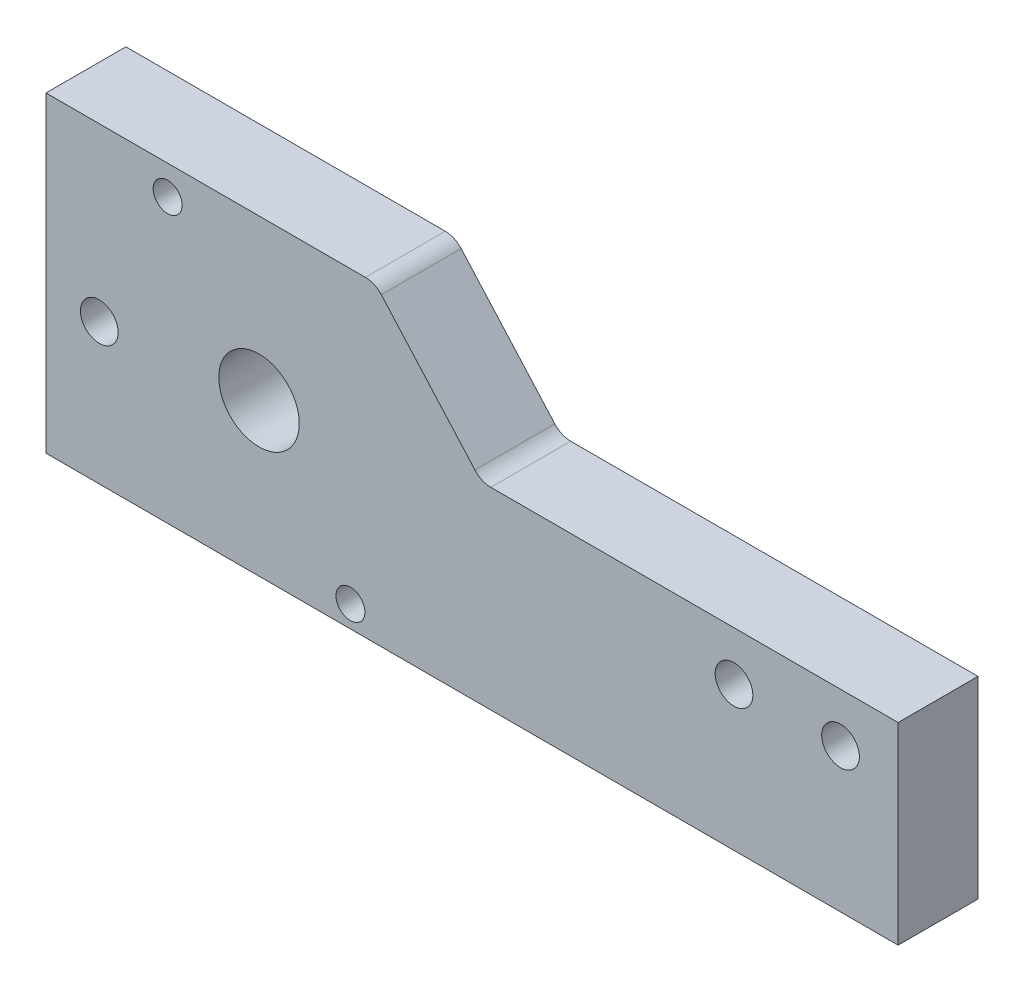
SolidWorks part; units mm, degrees
ref_plane "Front Plane" through (0, 0, 0) normal (0, 0, 1) x (1, 0, 0)
ref_plane "Top Plane" through (0, 0, 0) normal (0, 1, 0) x (1, 0, 0)
ref_plane "Right Plane" through (0, 0, 0) normal (1, 0, 0) x (0, 0, -1)
sketch "Sketch1" plane through (0, 0, 0) normal (0, 0, 1) x (1, 0, 0)
  line L1 (50.8, -25.4) -> (-50.8, -25.4)
  line L2 (50.8, -25.4) -> (50.8, 25.4)
  line L3 (50.8, 25.4) -> (-50.8, 25.4)
  line L4 (-50.8, -25.4) -> (-50.8, 25.4)
  line L5 (50.8, -25.4) -> (-50.8, 25.4) construction
  line L6 (50.8, 25.4) -> (-50.8, -25.4) construction
  point P0 (0, 0)
  dimension "D1" = 101.6
  dimension "D2" = 50.8
extrude "Boss-Extrude1" add sketch "Sketch1" along normal blind 9.525
sketch "Sketch3" plane through (0, 0, 9.525) normal (0, 0, 1) x (1, 0, 0)
  line L0 (-36.298, 21.9139) -> (-14.502, -9.2139) construction
  line L1 (50.8, 25.4) -> (-50.8, 25.4) construction
  circle A0 centre (-25.4, 6.35) radius 19 construction
  point P8 (-36.298, 21.9139)
  point P9 (-14.502, -9.2139)
  dimension "D1" = 38
  dimension "D2" = 25.4
  dimension "D3" = 6.35
  dimension "D4" = 55
sketch "Sketch6" plane through (0, 0, 0) normal (0, 0, 1) x (1, 0, 0)
  line L0 (-50.8, 25.4) -> (-50.8, -25.4) construction
  line L1 (-50.8, -25.4) -> (50.8, -25.4) construction
  circle A0 centre (-25.4, 6.35) radius 4.8 construction
  circle A1 centre (-25.4, 6.35) radius 4.8
  point P8 (-27.0981, 10.6379)
  point P9 (-20.85, 7.9694)
  dimension "D1" = 9.6
  dimension "D2" = 25.4
  dimension "D4" = 9.6
  dimension "D3" = 31.75
extrude "Cut-Extrude1" cut sketch "Sketch6" along normal through all contours A1
hole_wizard "Tap Drill for #8-32 Tap1" positions "Sketch3" profile "Sketch5" hole size "#8-32" standard "ANSI Inch" end condition through all
sketch "Sketch5" plane through (-14.502, -9.2139, 9.525) normal (1, 0, 0) x (0, -1, 0)
  line L0 (0, 0) -> (0, 9.525)
  line L1 (0, 9.525) -> (1.7272, 9.525)
  line L2 (1.7272, 9.525) -> (1.7272, 0)
  line L5 (1.7272, 0) -> (0, 0)
  line L11 (0, -6.35) -> (0, 107.95) construction
  dimension "Thru Hole Dia." = 3.4544
  dimension "Thru Hole Depth" = 9.525
sketch "Sketch7" plane through (0, 0, 0) normal (0, 0, -1) x (-1, 0, 0)
  line L0 (-50.8, -25.4) -> (-50.8, 25.4) construction
  line L1 (50.8, -25.4) -> (-50.8, -25.4)
  line L2 (50.8, -25.4) -> (50.8, -6.35)
  line L3 (50.8, -6.35) -> (-50.8, -6.35)
  line L4 (-50.8, -25.4) -> (-50.8, -6.35)
  dimension "D1" = 19.05
hole_wizard "#8 Clearance Hole1" positions "Sketch8" profile "Sketch9" hole size "#8" standard "ANSI Inch" end condition through all
sketch "Sketch8" plane through (0, 0, 9.525) normal (0, 0, 1) x (1, 0, 0)
  circle A0 centre (31.2318, 5.3435) radius 2.2479 construction
  circle A1 centre (43.9318, 5.3435) radius 2.2479 construction
  point P0 (31.2318, 5.3435)
  point P3 (43.9318, 5.3435)
sketch "Sketch9" plane through (31.2318, 5.3435, 9.525) normal (1, 0, 0) x (0, -1, 0)
  line L0 (0, 0) -> (0, 9.525)
  line L1 (0, 9.525) -> (2.2479, 9.525)
  line L2 (2.2479, 9.525) -> (2.2479, 0)
  line L5 (2.2479, 0) -> (0, 0)
  line L11 (0, -6.35) -> (0, 107.95) construction
  dimension "Thru Hole Dia." = 4.4958
  dimension "Thru Hole Depth" = 9.525
sketch "Sketch10" plane through (0, 0, 9.525) normal (0, 0, 1) x (1, 0, 0)
  line L0 (50.8, -25.4) -> (50.8, -6.35) construction
  line L1 (-50.8, -48.9404) -> (50.8, -48.9404)
  line L2 (-50.8, -48.9404) -> (-50.8, -11.8015)
  line L3 (-50.8, -11.8015) -> (50.8, -11.8015)
  line L4 (50.8, -48.9404) -> (50.8, -11.8015)
  line L5 (-50.8, -48.9404) -> (50.8, -11.8015) construction
  line L6 (-50.8, -11.8015) -> (50.8, -48.9404) construction
  point P0 (0, -30.371)
extrude "Cut-Extrude2" cut sketch "Sketch10" against normal through all
sketch "Sketch11" plane through (0, 0, 9.525) normal (0, 0, 1) x (1, 0, 0)
  line L0 (50.8, 11.1939) -> (1.0961, 11.1939)
  line L1 (50.8, -11.8015) -> (50.8, 25.4) construction
  line L2 (1.0961, 11.1939) -> (-11.5766, 25.4)
  line L3 (50.8, 25.4) -> (-50.8, 25.4) construction
  line L4 (50.8, 11.1939) -> (50.8, 25.4)
  line L5 (50.8, 25.4) -> (-11.5766, 25.4)
extrude "Cut-Extrude3" cut sketch "Sketch11" against normal through all
fillet "Fillet1" radius 2.54 2 edges at (1.0961, 11.1939, 4.7625) (-11.5766, 25.4, 4.7625)
sketch "Sketch12" plane through (0, 0, 9.525) normal (0, 0, 1) x (1, 0, 0)
  circle A0 centre (-44.45, 4.965) radius 2.2479
extrude "Cut-Extrude4" cut sketch "Sketch12" against normal through all
